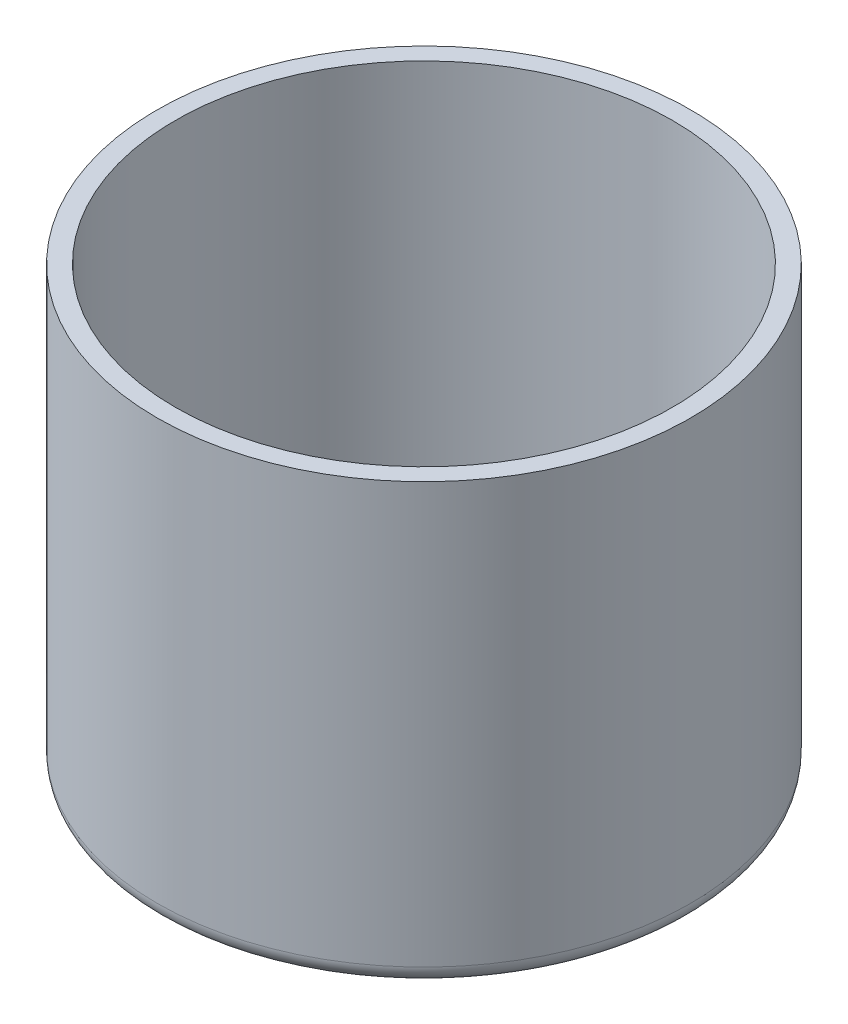
SolidWorks part; units mm, degrees
ref_plane "Front Plane" through (0, 0, 0) normal (0, 0, 1) x (1, 0, 0)
ref_plane "Top Plane" through (0, 0, 0) normal (0, 1, 0) x (1, 0, 0)
ref_plane "Right Plane" through (0, 0, 0) normal (1, 0, 0) x (0, 0, -1)
sketch "Sketch1" plane through (0, 0, 0) normal (0, 1, 0) x (1, 0, 0)
  circle A0 centre (0, 0) radius 68
  dimension "D1" = 136
extrude "Boss-Extrude1" add sketch "Sketch1" along normal blind 115
shell "Shell1" thickness 5 removed face at (0, 115, 68) outward yes
fillet "Fillet1" radius 5 1 edges at (0, -5, 73)
sketch "Sketch2" plane through (0, -5, 0) normal (0, -1, 0) x (1, 0, 0)
  circle A0 centre (0, 0) radius 40
extrude "Cut-Extrude1" cut sketch "Sketch2" against normal through all both and the other way through all contours A0
fillet "Fillet3" radius 2.5 2 edges at (0, 0, 40) (0, -5, 40)
